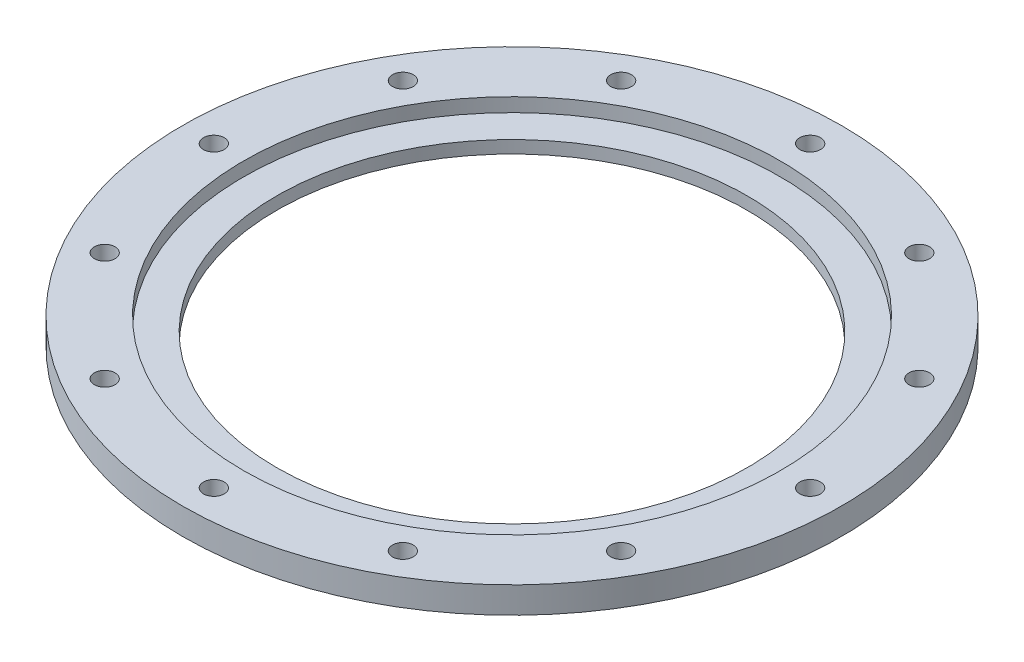
SolidWorks part; units mm, degrees
ref_plane "Front Plane" through (0, 0, 0) normal (0, 0, 1) x (1, 0, 0)
ref_plane "Top Plane" through (0, 0, 0) normal (0, 1, 0) x (1, 0, 0)
ref_plane "Right Plane" through (0, 0, 0) normal (1, 0, 0) x (0, 0, -1)
sketch "Sketch1" plane through (0, 0, 0) normal (0, 1, 0) x (1, 0, 0)
  circle A0 centre (0, 0) radius 37.5
  circle A1 centre (0, 0) radius 52.5
  dimension "D1" = 15
  dimension "D2" = 75
extrude "Boss-Extrude1" add sketch "Sketch1" along normal blind 2
sketch "Sketch2" plane through (0, 2, 0) normal (0, 1, 0) x (1, 0, 0)
  circle A0 centre (0, 0) radius 42.75
  circle A1 centre (0, 0) radius 52.5 construction
  circle A2 centre (0, 0) radius 52.5
  dimension "D1" = 85.5
extrude "Boss-Extrude2" add sketch "Sketch2" along normal blind 2.2
sketch "Sketch3" plane through (0, 0, 0) normal (0, -1, 0) x (1, 0, 0)
  line L0 (0, 0) -> (47.5, 0) construction
  circle A0 centre (0, 0) radius 47.5 construction
  circle A1 centre (0, 0) radius 52.5 construction
  circle A2 centre (47.5, 0) radius 1.65
  dimension "D1" = 5
  dimension "D2" = 3.3
extrude "Cut-Extrude1" cut sketch "Sketch3" against normal through all
pattern_circular "CirPattern1" count 12 over 360 about axis through (0, 0, 0) along (0, 1, 0) of "Cut-Extrude1"
